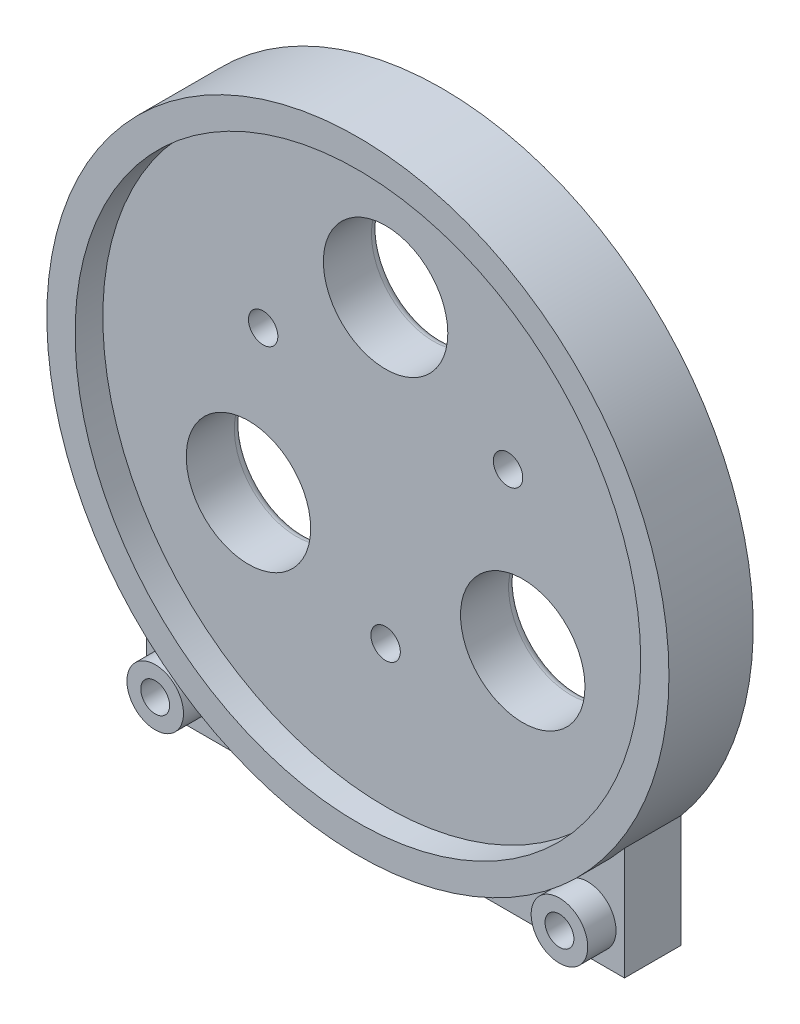
SolidWorks part; units mm, degrees
ref_plane "Ebene vorne" through (0, 0, 0) normal (0, 0, 1) x (1, 0, 0)
ref_plane "Ebene oben" through (0, 0, 0) normal (0, 1, 0) x (1, 0, 0)
ref_plane "Ebene rechts" through (0, 0, 0) normal (1, 0, 0) x (0, 0, -1)
sketch "Skizze1" plane through (0, 0, 0) normal (0, 0, 1) x (1, 0, 0)
  circle A0 centre (0, 0) radius 55
  dimension "D1" = 110
extrude "Aufsatz-Linear austragen1" add sketch "Skizze1" along normal blind 10
sketch "Skizze3" plane through (0, 0, 0) normal (0, 0, -1) x (-1, 0, 0)
  circle A0 centre (0, 28) radius 11
  dimension "D1" = 22
  dimension "D2" = 28
extrude "Schnitt-Linear austragen1" cut sketch "Skizze3" against normal blind 20 contours A0
pattern_circular "Kreismuster1" count 3 over 360 about axis through (0, 0, 0) along (0, 0, 1) of "Schnitt-Linear austragen1"
sketch "Skizze4" plane through (0, 0, 0) normal (0, 0, -1) x (-1, 0, 0)
  line L0 (-42.2388, -35.2262) -> (42.2388, -35.2262)
  line L1 (-42.2388, -35.2262) -> (-42.2388, -55.0978)
  line L2 (42.2388, -35.2262) -> (42.2388, -55.0978)
  line L3 (-42.2388, -55.0978) -> (42.2388, -55.0978)
  circle A0 centre (0, 0) radius 55 construction
extrude "Aufsatz-Linear austragen3" add sketch "Skizze4" against normal blind 10
sketch "Skizze5" plane through (0, -55.0978, 0) normal (0, -1, 0) x (1, 0, 0)
  line L0 (42.2388, 0) -> (-42.2388, 0) construction
  circle A0 centre (-20, 5) radius 2.2
  circle A1 centre (20, 5) radius 2.2
  dimension "D2" = 4.4
  dimension "D4" = 4.4
  dimension "D1" = 5
  dimension "D3" = 5
  dimension "D5" = 20
  dimension "D6" = 20
extrude "Schnitt-Linear austragen2" cut sketch "Skizze5" against normal blind 15
thread "Gewinde1" pitch 0.8 method cut profile "Gewindeprofil1" start angle 0, offset 0, length 15, pitch 0.8, diameter 4.4
ref_plane "Ebene1" through (22.2, -55.0978, 5) normal (0, 0, 1) x (1, 0, 0)
sketch "Gewindeprofil1" plane through (22.2, -55.0978, 5) normal (0, 0, 1) x (1, 0, 0)
  line L0 (0, 0) -> (0, 0.8) construction
  line L1 (0, 0) -> (0.433, 0.25)
  line L2 (0.433, 0.25) -> (0.433, 0.35)
  line L3 (0.433, 0.35) -> (0, 0.6)
  line L4 (0.433, 0.3) -> (0, 0.3) construction
  line L11 (0, 0) -> (0, 0.6)
  point P2 (0, 0)
  dimension "Pitch" = 0.8
  dimension "Profile_Angle" = 60
  dimension "Profile_Land" = 0.1
  dimension "Profile_Height" = 0.433
thread "Gewinde2" pitch 0.8 method cut profile "Gewindeprofil2" start angle 0, offset 0, length 15, pitch 0.8, diameter 4.4
ref_plane "Ebene2" through (-17.8, -55.0978, 5) normal (0, 0, 1) x (1, 0, 0)
sketch "Gewindeprofil2" plane through (-17.8, -55.0978, 5) normal (0, 0, 1) x (1, 0, 0)
  line L0 (0, 0) -> (0, 0.8) construction
  line L1 (0, 0) -> (0.433, 0.25)
  line L2 (0.433, 0.25) -> (0.433, 0.35)
  line L3 (0.433, 0.35) -> (0, 0.6)
  line L4 (0.433, 0.3) -> (0, 0.3) construction
  line L11 (0, 0) -> (0, 0.6)
  point P2 (0, 0)
  dimension "Pitch" = 0.8
  dimension "Profile_Angle" = 60
  dimension "Profile_Land" = 0.1
  dimension "Profile_Height" = 0.433
sketch "Skizze13" plane through (0, 0, 0) normal (0, 0, -1) x (-1, 0, 0)
  line L0 (-42.2388, -55.0978) -> (42.2388, -55.0978) construction
  line L1 (-42.2388, -35.2262) -> (-42.2388, -55.0978) construction
  line L2 (42.2388, -55.0978) -> (42.2388, -35.2262) construction
  circle A0 centre (-35.7388, -48.5978) radius 2.55
  circle A1 centre (35.7388, -48.5978) radius 2.55
  dimension "D5" = 5.1
  dimension "D6" = 5.1
  dimension "D1" = 6.5
  dimension "D2" = 6.5
  dimension "D3" = 6.5
  dimension "D4" = 6.5
extrude "Schnitt-Linear austragen4" cut sketch "Skizze13" against normal blind 10
fillet "Verrundung1" radius 1.5 3 edges at (29.7487, -4.4737, 0) (-18.7487, -23.5263, 0) (-11, 28, 0)
sketch "Skizze14" plane through (0, 0, 10) normal (0, 0, 1) x (1, 0, 0)
  circle A0 centre (0, 0) radius 55
  circle A1 centre (0, 0) radius 50
extrude "Aufsatz-Linear austragen4" add sketch "Skizze14" along normal blind 4.9
sketch "Skizze16" plane through (0, 0, 10) normal (0, 0, 1) x (1, 0, 0)
  circle A0 centre (-35.7388, -48.5978) radius 5
  circle A1 centre (35.7388, -48.5978) radius 5
  circle A2 centre (35.7388, -48.5978) radius 2.55
  circle A3 centre (-35.7388, -48.5978) radius 2.55
  dimension "D1" = 10
  dimension "D2" = 10
extrude "Aufsatz-Linear austragen7" add sketch "Skizze16" along normal blind 5
sketch "Skizze17" plane through (0, 0, 0) normal (0, 0, -1) x (-1, 0, 0)
  circle A0 centre (-35.7388, -48.5978) radius 4.5
  circle A1 centre (35.7388, -48.5978) radius 4.5
extrude "Schnitt-Linear austragen7" cut sketch "Skizze17" against normal blind 5
sketch "Skizze18" plane through (0, 0, 0) normal (0, 0, -1) x (-1, 0, 0)
  circle A0 centre (0, -25) radius 2.6
  dimension "D2" = 5.2
  dimension "D1" = 25
extrude "Schnitt-Linear austragen8" cut sketch "Skizze18" against normal blind 10
pattern_circular "Kreismuster2" count 3 over 360 about axis through (0, 0, 10) along (0, 0, -1) of "Schnitt-Linear austragen8" reverse direction yes
sketch "Skizze20" plane through (0, 0, 0) normal (0, 0, -1) x (-1, 0, 0)
  circle A0 centre (-21.6506, 12.5) radius 4.5
extrude "Schnitt-Linear austragen9" cut sketch "Skizze20" against normal blind 5
pattern_circular "Kreismuster3" count 3 over 360 about axis through (0, 0, 10) along (0, 0, -1) of "Schnitt-Linear austragen9"
